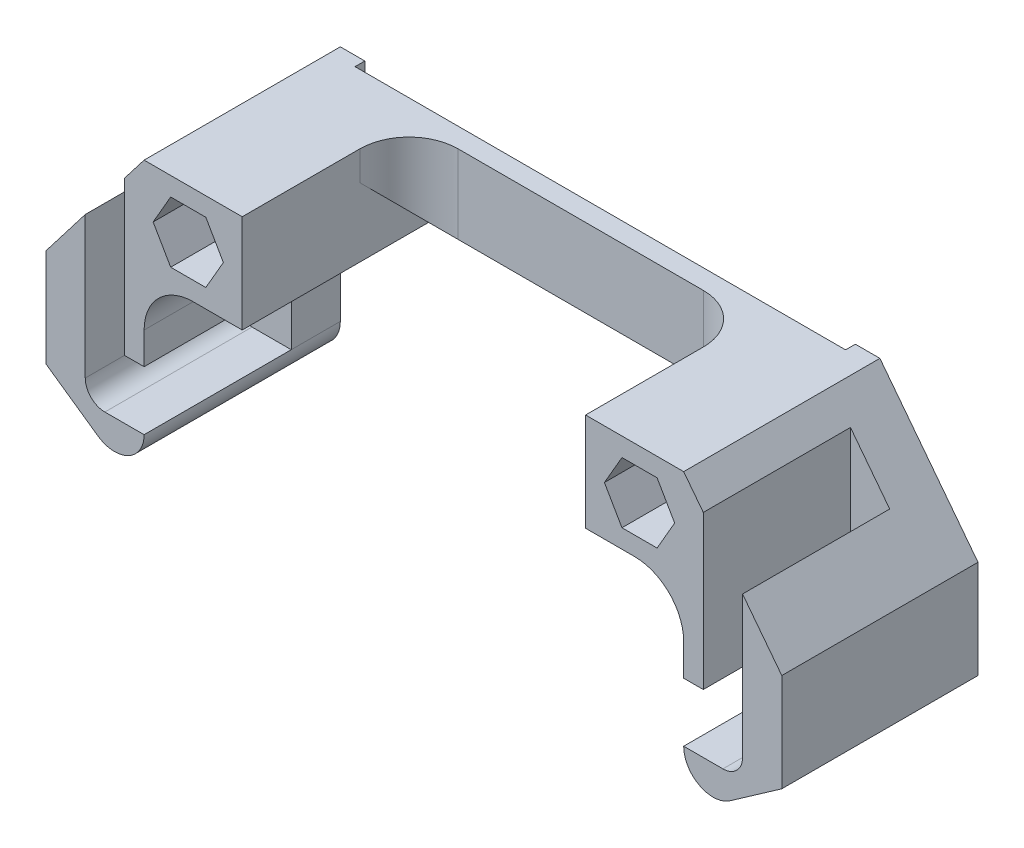
SolidWorks part; units mm, degrees
ref_plane "Front Plane" through (0, 0, 0) normal (0, 0, 1) x (1, 0, 0)
ref_plane "Top Plane" through (0, 0, 0) normal (0, 1, 0) x (1, 0, 0)
ref_plane "Right Plane" through (0, 0, 0) normal (1, 0, 0) x (0, 0, -1)
sketch "Sketch1" plane through (0, 0, 0) normal (0, 0, 1) x (1, 0, 0)
  line L0 (-22.5, 0) -> (22.5, 0)
  line L1 (27.5, -5) -> (27.5, -14.238)
  line L2 (32.2204, -16.6957) -> (37.5, -13)
  line L3 (37.5, -13) -> (37.5, -3)
  line L4 (37.5, -3) -> (27.5, 10)
  line L5 (27.5, 10) -> (-27.5, 10)
  line L6 (-27.5, 10) -> (-37.5, -3)
  line L7 (-37.5, -3) -> (-37.5, -13)
  line L8 (-37.5, -13) -> (-32.2204, -16.6957)
  line L9 (-27.5, -14.238) -> (-27.5, -5)
  line L10 (-27.5, 10) -> (-27.5, 0) construction
  line L11 (27.5, 10) -> (27.5, 0) construction
  line L12 (-37.5, -3) -> (37.5, -3) construction
  line L13 (0, -3) -> (0, 0) construction
  line L14 (-27.5, -20) -> (27.5, -20) construction
  line L15 (-37.5, -13) -> (37.5, -13) construction
  arc A0 (27.5, -14.238) -> (32.2204, -16.6957) centre (30.5, -14.238) ccw
  arc A1 (-32.2204, -16.6957) -> (-27.5, -14.238) centre (-30.5, -14.238) ccw
  arc A2 (22.5, 0) -> (27.5, -5) centre (22.5, -5) cw
  arc A3 (-22.5, 0) -> (-27.5, -5) centre (-22.5, -5) ccw
  dimension "D6" = 3
  dimension "D7" = 5
  dimension "D1" = 75
  dimension "D2" = 55
  dimension "D3" = 20
  dimension "D4" = 10
  dimension "D5" = 10
  dimension "D8" = 3
extrude "Boss-Extrude1" add sketch "Sketch1" along normal blind 20
sketch "Sketch3" plane through (0, 0, 0) normal (0, -1, 0) x (1, 0, 0)
  line L0 (-22.5, 20) -> (22.5, 20) construction
  line L1 (-17.5, 20) -> (17.5, 20)
  line L2 (-17.5, 20) -> (-17.5, 3)
  line L3 (-17.5, 3) -> (17.5, 3)
  line L4 (17.5, 20) -> (17.5, 3)
  line L5 (0, 3) -> (0, 0) construction
  line L6 (-22.5, 0) -> (22.5, 0) construction
  dimension "D1" = 35
  dimension "D2" = 3
extrude "Cut-Extrude2" cut sketch "Sketch3" against normal through all
sketch "Sketch2" plane through (0, 0, 20) normal (0, 0, 1) x (1, 0, 0)
  line L1 (-27.5, -14.238) -> (-30.5295, -14.238)
  line L2 (-27.5, -14.238) -> (-27.5, -8.238)
  line L3 (-27.5, -8.238) -> (-29.5, -8.238)
  line L5 (-30.5295, -14.238) -> (-31.5, -14.238)
  line L6 (-29.5, -8.238) -> (-29.5, 8.5948)
  line L7 (-29.5, 8.5948) -> (-33.5, 8.5948)
  line L8 (-33.5, -12.238) -> (-33.5, 8.5948)
  arc A0 (-31.5, -14.238) -> (-33.5, -12.238) centre (-31.5, -12.238) cw
  dimension "D4" = 2
  dimension "D1" = 6
  dimension "D2" = 4
  dimension "D3" = 2
extrude "Cut-Extrude1" cut sketch "Sketch2" against normal blind 15
mirror "Mirror1" about plane through (0, 0, 0) normal (1, 0, 0) of "Cut-Extrude1"
sketch "Sketch4" plane through (0, 0, 0) normal (0, 0, -1) x (-1, 0, 0)
  line L0 (0, -4.4474) -> (0, 0) construction
  line L1 (-25, 12.7316) -> (25, 12.7316)
  line L2 (-25, 12.7316) -> (-25, -4.4474)
  line L3 (-25, -4.4474) -> (25, -4.4474)
  line L4 (25, 12.7316) -> (25, -4.4474)
  dimension "D1" = 50
extrude "Cut-Extrude3" cut sketch "Sketch4" against normal blind 1
sketch "Sketch5" plane through (0, 0, 20) normal (0, 0, 1) x (1, 0, 0)
  line L0 (-23, 5) -> (23, 5) construction
  line L1 (0, 5) -> (0, 0) construction
  circle A0 centre (-23, 5) radius 1.75
  circle A1 centre (23, 5) radius 1.75
  dimension "D3" = 3.5
  dimension "D1" = 5
  dimension "D2" = 46
extrude "Cut-Extrude4" cut sketch "Sketch5" against normal through all
sketch "Sketch6" plane through (0, 0, 20) normal (0, 0, 1) x (1, 0, 0)
  line L1 (-19.4204, 5) -> (-21.2102, 8.1)
  line L2 (-21.2102, 8.1) -> (-24.7898, 8.1)
  line L3 (-24.7898, 8.1) -> (-26.5796, 5)
  line L4 (-26.5796, 5) -> (-24.7898, 1.9)
  line L5 (-24.7898, 1.9) -> (-21.2102, 1.9)
  line L6 (-21.2102, 1.9) -> (-19.4204, 5)
  line L7 (19.4204, 5) -> (21.2102, 1.9)
  line L8 (21.2102, 1.9) -> (24.7898, 1.9)
  line L9 (24.7898, 1.9) -> (26.5796, 5)
  line L10 (26.5796, 5) -> (24.7898, 8.1)
  line L11 (24.7898, 8.1) -> (21.2102, 8.1)
  line L12 (21.2102, 8.1) -> (19.4204, 5)
  circle A0 centre (-23, 5) radius 3.1 construction
  circle A1 centre (23, 5) radius 3.1 construction
  dimension "D1" = 6.2
extrude "Cut-Extrude5" cut sketch "Sketch6" against normal blind 15
chamfer "Chamfer1" distance 2 angle 45 1 edges at (0, 0, 3)
fillet "Fillet1" radius 5 2 edges at (17.5, 6, 3) (-17.5, 6, 3)
